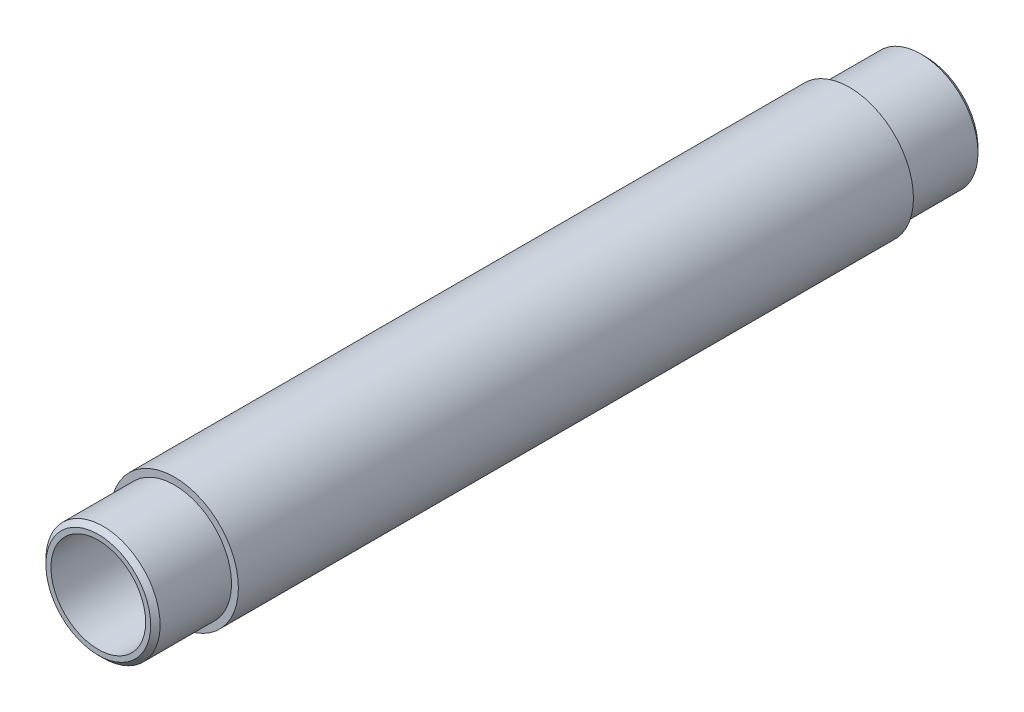
SolidWorks part; units mm, degrees
material "Plain Carbon Steel"
ref_plane "Front Plane" through (0, 0, 0) normal (0, 0, 1) x (1, 0, 0)
ref_plane "Top Plane" through (0, 0, 0) normal (0, 1, 0) x (1, 0, 0)
ref_plane "Right Plane" through (0, 0, 0) normal (1, 0, 0) x (0, 0, -1)
sketch "Sketch1" plane through (0, 0, 0) normal (0, 0, 1) x (1, 0, 0)
  circle A0 centre (0, 0) radius 10.668
  circle A1 centre (0, 0) radius 7.8994
  dimension "D1" = 21.336
  dimension "D2" = 2.7686
extrude "Boss-Extrude1" add sketch "Sketch1" along normal blind 69 and the other way blind 69
sketch "Sketch2" plane through (0, 0, 69) normal (0, 0, 1) x (1, 0, 0)
  circle A0 centre (0, 0) radius 15.2323
  circle A1 centre (0, 0) radius 9.525
  dimension "D1" = 19.05
extrude "Cut-Extrude1" cut sketch "Sketch2" against normal blind 12.7
sketch "Sketch3" plane through (0, 0, -69) normal (0, 0, -1) x (-1, 0, 0)
  circle A3 centre (0, 0) radius 9.525
  circle A4 centre (0, 0) radius 9.525
  circle A5 centre (0, 0) radius 15.2323
  circle A6 centre (0, 0) radius 15.2323
  dimension "D1" = 0
  dimension "D2" = 0
extrude "Cut-Extrude2" cut sketch "Sketch3" against normal blind 12.7
chamfer "Chamfer1" distance 0.7874 angle 45 2 edges at (9.525, 0, 69) (-9.525, 0, -69)
sketch3d "3DSketch1"
  line L0 (0, 0, 69) -> (0, 0, -69) construction
  line L1 (0, 0, -69) -> (0, 0, 69) construction
  line L2 (0, 0, 68.2126) -> (0, 0, 69) construction
